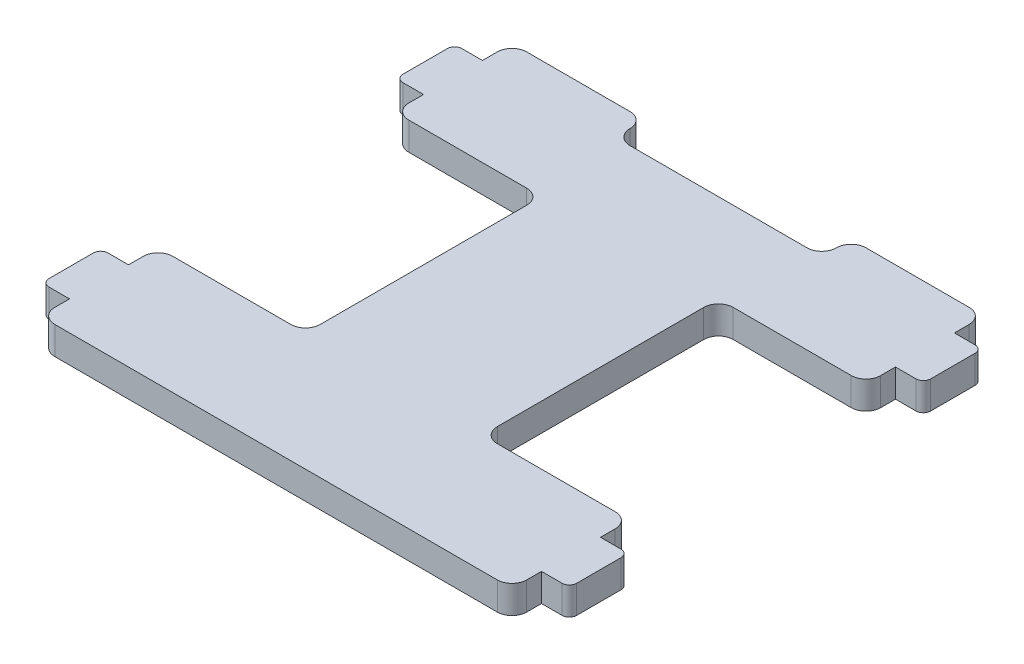
SolidWorks part; units mm, degrees
ref_plane "Front Plane" through (0, 0, 0) normal (0, 0, 1) x (1, 0, 0)
ref_plane "Top Plane" through (0, 0, 0) normal (0, 1, 0) x (1, 0, 0)
ref_plane "Right Plane" through (0, 0, 0) normal (1, 0, 0) x (0, 0, -1)
sketch "Sketch1" plane through (0, 0, 0) normal (0, 1, 0) x (1, 0, 0)
  line L0 (25.4, 12.7) -> (9.525, 12.7)
  line L1 (-25.4, -25.4) -> (-9.525, -25.4)
  line L2 (-25.4, -25.4) -> (-25.4, -12.7)
  line L3 (-25.4, 25.4) -> (-11.1125, 25.4)
  line L4 (25.4, -25.4) -> (25.4, -12.7)
  line L5 (-25.4, -25.4) -> (25.4, 25.4) construction
  line L6 (-25.4, 25.4) -> (25.4, -25.4) construction
  line L7 (9.525, 12.7) -> (9.525, -12.7)
  line L8 (9.525, -12.7) -> (25.4, -12.7)
  line L9 (-25.4, -12.7) -> (-9.525, -12.7)
  line L10 (-9.525, -12.7) -> (-9.525, 12.7)
  line L11 (-9.525, 12.7) -> (-25.4, 12.7)
  line L12 (0, -25.4) -> (0, 25.4) construction
  line L13 (-25.4, -12.7) -> (-25.4, 12.7) construction
  line L14 (-25.4, 12.7) -> (-25.4, 25.4)
  line L15 (25.4, -12.7) -> (25.4, 12.7) construction
  line L16 (25.4, 12.7) -> (25.4, 25.4)
  line L20 (0, -25.4) -> (9.525, -25.4)
  line L21 (9.525, -25.4) -> (25.4, -25.4)
  line L22 (-9.525, -25.4) -> (0, -25.4)
  line L23 (-11.1125, 25.4) -> (-11.1125, 22.225)
  line L24 (-11.1125, 22.225) -> (11.1125, 22.225)
  line L25 (11.1125, 22.225) -> (11.1125, 25.4)
  line L26 (-11.1125, 25.4) -> (0, 25.4) construction
  line L27 (11.1125, 25.4) -> (25.4, 25.4)
  line L28 (0, 25.4) -> (11.1125, 25.4) construction
  point P0 (0, 0)
  dimension "D1" = 50.8
  dimension "D2" = 50.8
  dimension "D3" = 12.7
  dimension "D4" = 12.7
  dimension "D5" = 19.05
  dimension "D6" = 22.225
  dimension "D7" = 3.175
extrude "Boss-Extrude1" add sketch "Sketch1" along normal mid plane 3
fillet "Fillet1" radius 1.5875 16 edges at (25.4, 0, -12.7) (9.525, 0, -12.7) (9.525, 0, 12.7) (25.4, 0, 12.7) (25.4, 0, 25.4) (-25.4, 0, 12.7) (-9.525, 0, 12.7) (-9.525, 0, -12.7) (-25.4, 0, -12.7) (-25.4, 0, -25.4) (-25.4, 0, 25.4) (25.4, 0, -25.4) (-11.1125, 0, -25.4) (-11.1125, 0, -22.225) (11.1125, 0, -22.225) (11.1125, 0, -25.4)
sketch "Sketch2" plane through (0, 1.5, 0) normal (0, 1, 0) x (1, 0, 0)
  line L5 (-25.4, 12.7) -> (-25.4, 25.4) construction
  line L6 (-26.9, 19.05) -> (-25.4, 19.05) construction
  line L12 (-25.4, -25.4) -> (-25.4, -12.7) construction
  line L13 (25.4, 12.7) -> (25.4, 25.4) construction
  line L14 (25.4, -25.4) -> (25.4, -12.7) construction
  line L15 (-26.9, -19.05) -> (-25.4, -19.05) construction
  line B0 (-28.4, 15.875) -> (-25.4, 15.875)
  line B1 (-28.4, 15.875) -> (-28.4, 22.225)
  line B2 (-28.4, 22.225) -> (-25.4, 22.225)
  line B3 (-25.4, 15.875) -> (-25.4, 22.225)
  line B4 (-28.4, 15.875) -> (-25.4, 22.225) construction
  line B5 (-28.4, 22.225) -> (-25.4, 15.875) construction
  line B6 (25.4, 15.875) -> (28.4, 15.875)
  line B7 (25.4, 15.875) -> (25.4, 22.225)
  line B8 (25.4, 22.225) -> (28.4, 22.225)
  line B9 (28.4, 15.875) -> (28.4, 22.225)
  line B10 (25.4, -22.225) -> (28.4, -22.225)
  line B11 (25.4, -22.225) -> (25.4, -15.875)
  line B12 (25.4, -15.875) -> (28.4, -15.875)
  line B13 (28.4, -22.225) -> (28.4, -15.875)
  line B14 (-28.4, -22.225) -> (-25.4, -22.225)
  line B15 (-28.4, -22.225) -> (-28.4, -15.875)
  line B16 (-28.4, -15.875) -> (-25.4, -15.875)
  line B17 (-25.4, -22.225) -> (-25.4, -15.875)
sketch_block_instance "Block1-1"
sketch_block "Block1" parameters "D1"=6.35, "D2"=3
sketch_block_instance "Block1-2"
sketch_block_instance "Block1-3"
sketch_block_instance "Block1-4"
extrude "Boss-Extrude2" add sketch "Sketch2" against normal up to surface (3 mm away) up to face at (0, -1.5, -4.7625)
fillet "Fillet2" radius 0.7937 8 edges at (-28.4, 0, 22.225) (-28.4, 0, 15.875) (28.4, 0, 15.875) (28.4, 0, 22.225) (28.4, 0, -22.225) (28.4, 0, -15.875) (-28.4, 0, -22.225) (-28.4, 0, -15.875)
